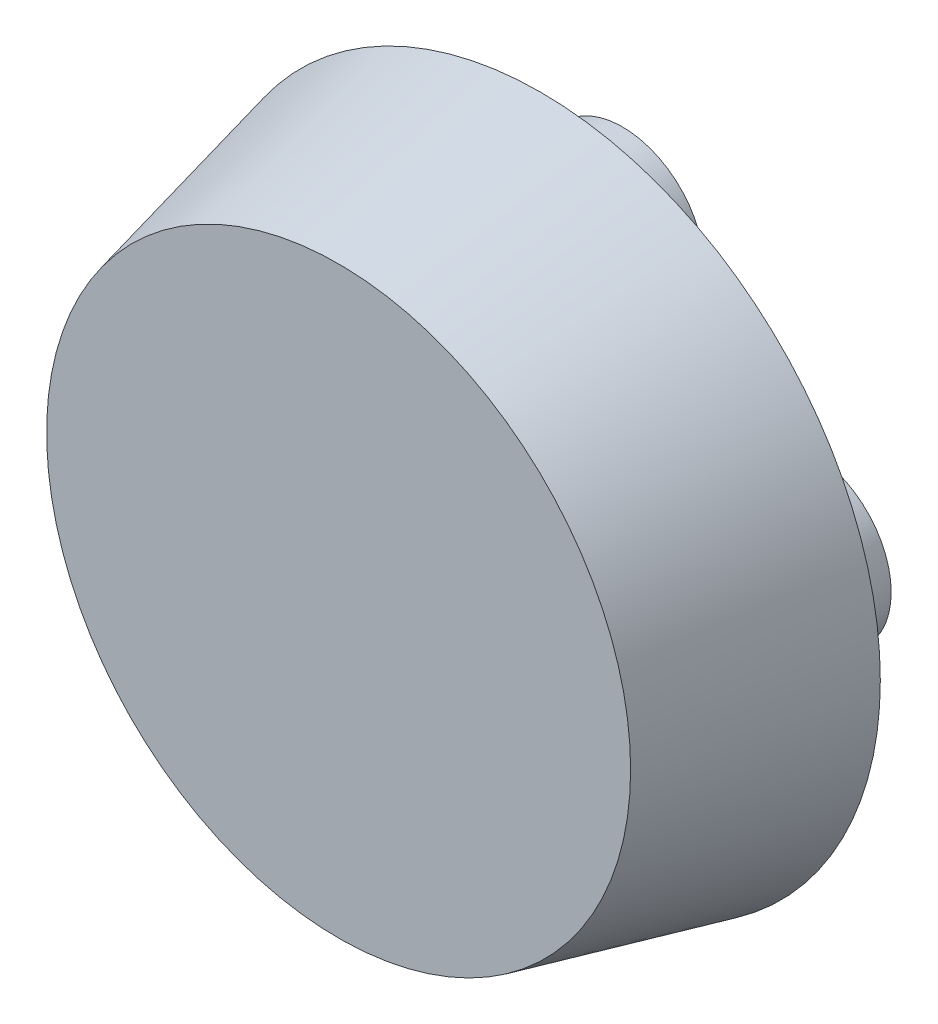
SolidWorks part; units mm, degrees
ref_plane "Front Plane" through (0, 0, 0) normal (0, 0, 1) x (1, 0, 0)
ref_plane "Top Plane" through (0, 0, 0) normal (0, 1, 0) x (1, 0, 0)
ref_plane "Right Plane" through (0, 0, 0) normal (1, 0, 0) x (0, 0, -1)
sketch "Big Plug Sketch" plane through (0, 0, 0) normal (1, 0, 0) x (0, 0, -1)
  line L0 (594.1751, -558.8643) -> (886.5863, -558.8643) construction
  line L1 (0, 0) -> (531.6016, 125) construction
  line L2 (0, 0) -> (531.6016, 0) construction
  line L3 (531.6016, 125) -> (531.6016, 0)
  line L4 (531.6016, 125) -> (618.1413, 145.3488)
  line L5 (531.6016, 0) -> (635, 0)
  arc A1 (635, 0) -> (618.1413, 145.3488) centre (0, 0) ccw
  dimension "D1" = 546.1
  dimension "D2" = 635
  dimension "D3" = 125
revolve "Big Plug" add sketch "Big Plug Sketch" angle 360 about L2
ref_plane "Big Plug Subsurface Plane" through (0, 0, -618.1413) normal (0, 0, 1) x (1, 0, 0)
sketch "Cables Sketch" plane through (0, 0, -618.1413) normal (0, 0, 1) x (1, 0, 0)
  line L0 (0, 145.3488) -> (0, -145.3488) construction
  line L1 (145.3488, 0) -> (-145.3488, 0) construction
  line L2 (0, 80) -> (0, 0) construction
  line L3 (0, 145.3488) -> (145.3488, 0) construction
  line L4 (145.3488, 0) -> (0, -145.3488) construction
  line L7 (72.6744, 72.6744) -> (0, 0) construction
  line L8 (0, 0) -> (72.6744, -72.6744) construction
  circle A0 centre (0, 0) radius 145.3488 construction
  circle A1 centre (0, 80) radius 35
  circle A2 centre (0, 80) radius 35
  circle A5 centre (80, 0) radius 35
  circle A6 centre (0, -80) radius 35
  circle A7 centre (-80, 0) radius 35
  point P12 (0, 0)
  dimension "D1" = 70
  dimension "D2" = 80
extrude "Cables" add sketch "Cables Sketch" against normal blind 35 from surface contours A1 | A5 | A6 | A7 starting at plane "Big Plug Subsurface Plane"
